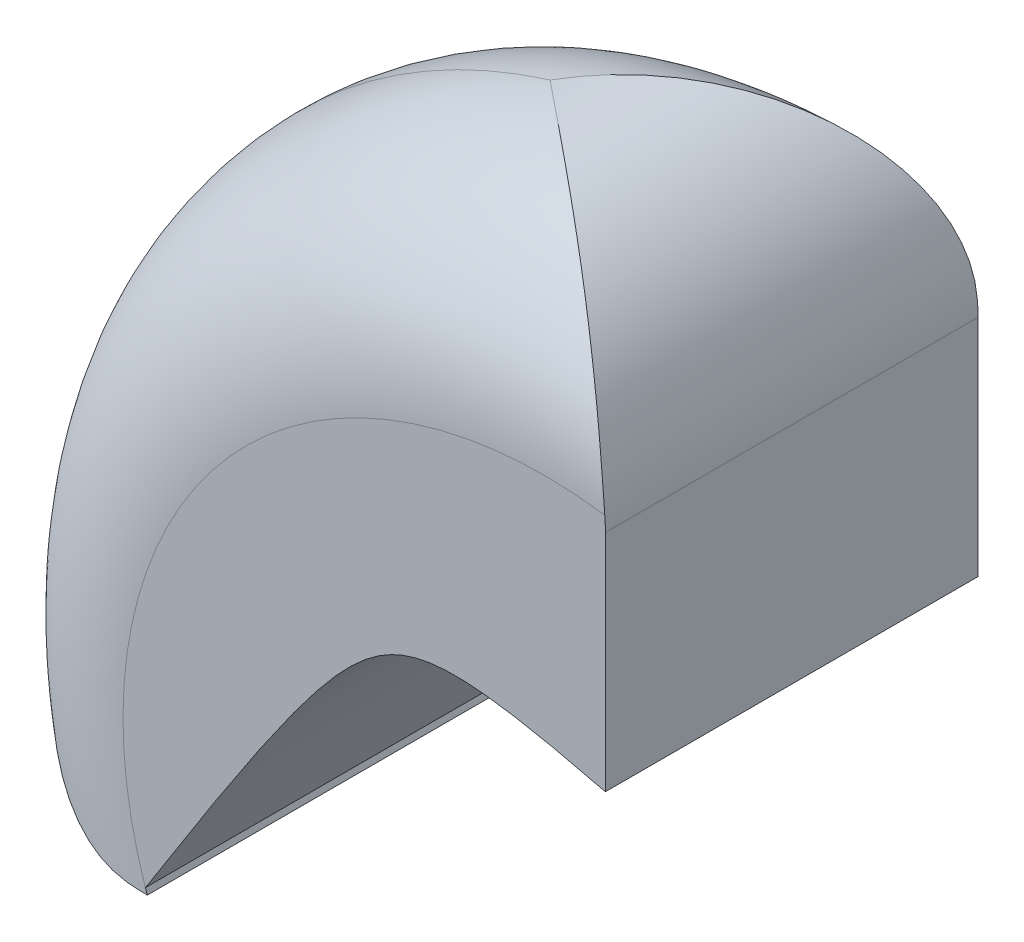
SolidWorks part; units mm, degrees
ref_plane "Front Plane" through (0, 0, 0) normal (0, 0, 1) x (1, 0, 0)
ref_plane "Top Plane" through (0, 0, 0) normal (0, 1, 0) x (1, 0, 0)
ref_plane "Right Plane" through (0, 0, 0) normal (1, 0, 0) x (0, 0, -1)
sketch "Sketch2" plane through (0, 0, 0) normal (0, 0, 1) x (1, 0, 0)
  line L0 (0, 0) -> (-8.89, 0)
  line L1 (0, 0) -> (0, 10.16)
  arc A0 (-8.89, 0) -> (0, 10.16) centre (-0.837, 1.923) cw
  dimension "D1" = 10.16
  dimension "D2" = 8.89
extrude "Boss-Extrude1" add sketch "Sketch2" along normal blind 5.08
fillet "Fillet1" radius 2.54 4 edges at (0, 10.16, 2.54) (-7.0679, 7.375, 5.08) (-8.89, 0, 2.54) (-7.0679, 7.375, 0)
sketch "Sketch4" plane through (0, 0, 0) normal (0, 0, 1) x (1, 0, 0)
  line L0 (0, -3.0174) -> (0, 3.0174) construction
  line L1 (0, 4.3425) -> (0, 0)
  line L2 (0, 0) -> (-6.2447, 0)
  line L3 (-6.2447, 0) -> (-6.2708, 0.0751)
  arc A0 (-0.0077, 7.6022) -> (-6.2447, 0) centre (-0.837, 1.923) ccw construction
  conic Q0 (-6.2708, 0.0751) -> (0, 4.3425) control (-3.1058, 5.1134) rho 0.75
extrude "Cut-Extrude1" cut sketch "Sketch4" along normal blind 5.08 contours Q0 L1 L2 L3
